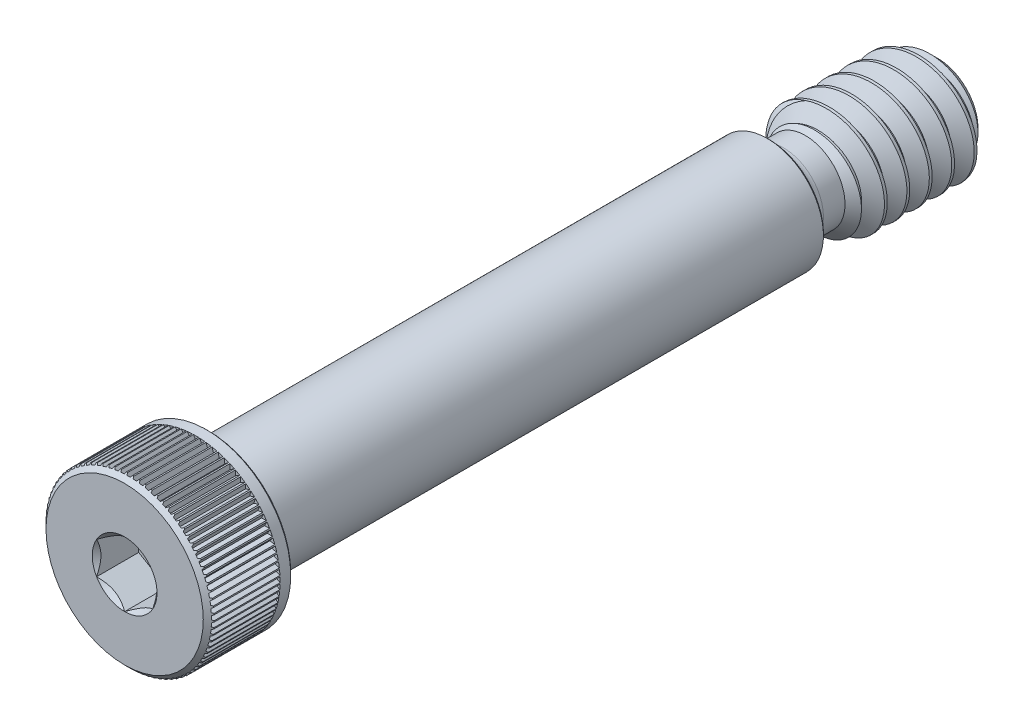
SolidWorks part; units mm, degrees
ref_plane "Front Plane" through (0, 0, 0) normal (0, 0, 1) x (1, 0, 0)
ref_plane "Top Plane" through (0, 0, 0) normal (0, 1, 0) x (1, 0, 0)
ref_plane "Right Plane" through (0, 0, 0) normal (1, 0, 0) x (0, 0, -1)
sketch "Sketch1" plane through (0, 0, 0) normal (1, 0, 0) x (0, 0, -1)
  line L0 (0, 0) -> (9.525, 0) construction
  line L1 (0, 0) -> (-31.75, 0) construction
  line L2 (9.525, 3.175) -> (9.525, -3.175) construction
  line L3 (9.4456, 3.3125) -> (10.7156, 3.3125) construction
  line L4 (10.7156, 3.3125) -> (10.0806, 2.2126) construction
  line L5 (10.0806, 2.2126) -> (9.4456, 3.3125) construction
  line L6 (9.4853, 3.2437) -> (10.6759, 3.2437) construction
  line L7 (9.525, 3.175) -> (10.6363, 3.175) construction
  line L8 (10.0012, 2.3501) -> (10.16, 2.3501) construction
  line L9 (10.0806, 2.3501) -> (10.0806, 2.2126) construction
  line L10 (10.0806, 3.175) -> (10.0806, 3.3125) construction
  line L11 (0, 3.175) -> (0, -3.175) construction
  line L12 (-31.75, 0) -> (-36.5125, 0) construction
  line L13 (-36.5125, 4.7625) -> (-36.5125, -4.7625) construction
  line L14 (-31.75, 4.7625) -> (-31.75, -4.7625) construction
  point P7 (9.525, 0)
  point P12 (6.35, -3.175)
  point P19 (10.0806, 3.2437)
  point P23 (0, 0)
  point P27 (-36.5125, 0)
  point P29 (-31.75, 0)
  point P30 (-36.5125, -1.5875)
  point P31 (-36.5125, 1.5875)
  point P32 (9.525, 3.175)
  point P33 (-34.1313, 0)
  point P34 (9.525, -3.175)
  dimension "Screw Size Decimal Equivalent" = 6.35
  dimension "D1" = 60
  dimension "Pitch" = 1.27
  dimension "D2" = 0.1588
  dimension "Thread Length" = 9.525
  dimension "D3" = 3.175
  dimension "Head Diameter" = 9.525
  dimension "Head Height" = 4.7625
  dimension "Shoulder Length" = 31.75
  dimension "Drive Size" = 3.175
  dimension "D4" = 2.3813
  dimension "Shoulder Diameter" = 6.35
sketch "Sketch2" plane through (0, 0, 0) normal (1, 0, 0) x (0, 0, -1)
  line L0 (0, 3.175) -> (2.9591, 3.175) construction
  line L1 (2.9591, 3.175) -> (2.032, 2.2479) construction
  line L2 (2.032, 2.2479) -> (0, 2.2479) construction
  line L3 (0, 0) -> (9.525, 0) construction
  line L4 (0, 0) -> (9.525, 0) construction
  line L6 (0, 3.175) -> (0, -3.175) construction
  dimension "Thread Neck (Undercut) Width/Length" = 2.032
  dimension "D3" = 45
  dimension "Thread Neck (Undercut) Diameter" = 4.4958
sketch "Sketch3" plane through (0, 0, 0) normal (1, 0, 0) x (0, 0, -1)
  line L0 (-36.5125, 4.4529) -> (-36.2029, 4.7625)
  line L1 (-36.5125, 4.7625) -> (-36.5125, -4.7625) construction
  line L2 (-36.2029, 4.7625) -> (-31.8691, 4.7625)
  line L3 (-31.8691, 4.7625) -> (-31.75, 4.6434)
  line L4 (-31.75, 4.6434) -> (-31.75, 3.175)
  line L5 (-36.5125, 4.4529) -> (-36.5125, 0)
  line L6 (-36.5125, 0) -> (-31.2738, 0)
  line L7 (0, 0) -> (-31.75, 0) construction
  line L8 (-31.2738, 0) -> (-31.2738, 3.175)
  line L9 (-31.2738, 3.175) -> (-31.75, 3.175)
  line L10 (0, 0) -> (-31.75, 0) construction
  dimension "D1" = 45
  dimension "D2" = 0.3096
  dimension "D3" = 45
  dimension "D4" = 0.1191
  dimension "D5" = 0.4763
  dimension "D6" = 6.35
revolve "Revolve1" add sketch "Sketch3" angle 360 about L6
fillet "Fillet1" radius 0.127 1 edges at (3.175, 0, 31.75)
sketch "Sketch4" plane through (0, 0, 0) normal (1, 0, 0) x (0, 0, -1)
  line L0 (-31.2738, 3.175) -> (-0.1191, 3.175)
  line L1 (0, 3.0559) -> (0, 0)
  line L2 (0, 0) -> (-31.2738, 0)
  line L3 (-31.2738, 0) -> (-31.2738, 3.175)
  line L4 (-0.1191, 3.175) -> (0, 3.0559)
  dimension "D1" = 45
  dimension "D2" = 0.1191
revolve "Revolve2" add sketch "Sketch4" angle 360 about L2
sketch "Sketch5" plane through (0, 0, 0) normal (1, 0, 0) x (0, 0, -1)
  line L0 (9.525, 2.286) -> (8.636, 3.175)
  line L1 (9.525, 3.175) -> (9.525, -3.175) construction
  line L2 (8.636, 3.175) -> (2.9591, 3.175)
  line L3 (2.9591, 3.175) -> (2.032, 2.2479)
  line L4 (2.032, 2.2479) -> (0.808, 2.2479)
  line L5 (0, 3.0559) -> (0, 0)
  line L6 (0, 3.175) -> (0, -3.175) construction
  line L7 (0, 0) -> (9.525, 0)
  line L8 (9.525, 0) -> (9.525, 2.286)
  line L9 (2.032, 2.2479) -> (0, 2.2479) construction
  arc A1 (0.808, 2.2479) -> (0, 3.0559) centre (0.808, 3.0559) cw
  dimension "D1" = 45
  dimension "D2" = 0.889
revolve "Revolve3" add sketch "Sketch5" angle 360 about L7
sketch "Sketch6" plane through (0, 0, 36.5125) normal (0, 0, 1) x (1, 0, 0)
  line L1 (-1.5875, 0.9165) -> (-1.5875, -0.9165)
  line L2 (-1.5875, -0.9165) -> (0, -1.8331)
  line L3 (0, -1.8331) -> (1.5875, -0.9165)
  line L4 (1.5875, -0.9165) -> (1.5875, 0.9165)
  line L5 (1.5875, 0.9165) -> (0, 1.8331)
  line L6 (0, 1.8331) -> (-1.5875, 0.9165)
  circle A0 centre (0, 0) radius 1.5875 construction
extrude "Cut-Extrude1" cut sketch "Sketch6" against normal up to vertex (2.3813 mm away) up to point (0, 0, 34.1313)
sketch "Sketch7" plane through (0, 0, 36.5125) normal (0, 0, 1) x (1, 0, 0)
  circle A0 centre (0, 0) radius 1.8331
extrude "Cut-Extrude2" cut sketch "Sketch7" against normal up to vertex (2.3813 mm away) draft 45 up to point (0, 0, 34.1313)
sketch "Sketch11" plane through (0, 0, 34.1313) normal (0, 0, 1) x (1, 0, 0)
  line L1 (-0.5556, 0.3208) -> (-0.5556, -0.3208)
  line L2 (-0.5556, -0.3208) -> (0, -0.6416)
  line L3 (0, -0.6416) -> (0.5556, -0.3208)
  line L4 (0.5556, -0.3208) -> (0.5556, 0.3208)
  line L5 (0.5556, 0.3208) -> (0, 0.6416)
  line L6 (0, 0.6416) -> (-0.5556, 0.3208)
  circle A0 centre (0, 0) radius 0.5556 construction
  dimension "D1" = 1.1113
extrude "Cut-Extrude4" cut sketch "Sketch11" against normal blind 1.1906 draft 45
sketch "Sketch12" plane through (0, 0, 0) normal (1, 0, 0) x (0, 0, -1)
  line L0 (-23.8125, 4.7625) -> (-23.8125, -4.7625) construction
  line L2 (-7.9375, 4.7625) -> (-7.9375, -4.7625) construction
  line L4 (-31.75, 4.7625) -> (-31.75, -4.7625) construction
  line L5 (0, 0) -> (-31.75, 0) construction
  line L7 (0, 3.175) -> (0, -3.175) construction
  point P3 (-23.8125, 0)
  point P6 (-7.9375, 0)
  dimension "D1" = 7.9375
  dimension "D2" = 7.9375
sketch "Sketch13" plane through (0, 0, 0) normal (0, 0, 1) x (1, 0, 0)
  circle A0 centre (0, 0) radius 4.7625 construction
sketch "Sketch8" plane through (0, 0, 0) normal (1, 0, 0) x (0, 0, -1)
  line L0 (9.4853, 3.2437) -> (10.6759, 3.2437)
  line L1 (10.6759, 3.2437) -> (10.16, 2.3501)
  line L2 (10.16, 2.3501) -> (10.0012, 2.3501)
  line L3 (10.0012, 2.3501) -> (9.4853, 3.2437)
sketch "Sketch9" plane through (0, 0, -9.525) normal (0, 0, -1) x (-1, 0, 0)
  circle A0 centre (0, 0) radius 3.175
curve "Helix/Spiral1" pitch 1.27 height 9.525 radius 3.175 centre (0, 0, -9.525) axis (0, 0, 1) start towards (0, 1, 0)
sweep "Cut-Sweep1" cut profiles "Sketch8" path "Helix/Spiral1"
ref_plane "Plane1" through (0, 0, 36.2803) normal (0, 0, 1) x (1, 0, 0)
sketch "Sketch10" plane through (0, 0, 36.2803) normal (0, 0, 1) x (1, 0, 0)
  line L0 (-0.143, 4.7625) -> (0.143, 4.7625)
  line L1 (-0.143, 4.7625) -> (0, 4.5149)
  line L2 (0, 4.5149) -> (0.143, 4.7625)
  line L3 (-0.143, 4.7625) -> (0, 0) construction
  line L4 (0, 0) -> (0.143, 4.7625) construction
  circle A0 centre (0, 0) radius 4.5149 construction
  point P7 (0, 4.7625)
  dimension "D1" = 0.2476
  dimension "D2" = 3.439
extrude "Cut-Extrude3" cut sketch "Sketch10" against normal blind 3.81
pattern_circular "CirPattern1" count 85 over 360 about axis through (0, 0, 31.75) along (0, 0, 1) of "Cut-Extrude3" reverse direction yes
equation "\"D2@Sketch1\"=\"Pitch@Sketch1\"/8"
equation "\"D3@Sketch1\"=\"Pitch@Sketch1\"*2.5"
equation "\"D4@Sketch1\"=\"Head Height@Sketch1\"*.5"
equation "\"D2@Sketch3\"=\"Head Height@Sketch1\" * .065"
equation "\"D4@Sketch3\" = \"Head Height@Sketch1\" * .025"
equation "\"D5@Sketch3\"=\"Head Height@Sketch1\"*.1"
equation "\"D1@Fillet1\"=\"Shoulder Diameter@Sketch1\"*.02"
equation "\"D2@Sketch5\"=\"Pitch@Sketch1\"*.7"
equation "\"D2@Sketch4\"=\"D4@Sketch3\""
equation "\"D3@Helix/Spiral1\"=\"Thread Length@Sketch1\""
equation "\"D4@Helix/Spiral1\"=\"Pitch@Sketch1\""
equation "\"D1@Sketch10\"=\"D2@Sketch3\"*.8"
equation "\"D1@Cut-Extrude3\"=\"Head Height@Sketch1\"*.8"
equation "\"D1@CirPattern1\"=(360/\"D2@Sketch10\")-20"
equation "\"D1@Plane1\"=\"D2@Sketch3\"*.75"
equation "\"D1@Sketch11\"=\"Drive Size@Sketch1\"*.35"
equation "\"D1@Cut-Extrude4\"=\"Head Height@Sketch1\"*.25"
equation "\"D1@Sketch12\"=\"Shoulder Length@Sketch1\"*.25"
equation "\"D2@Sketch12\"=\"D1@Sketch12\""
equation "\"D6@Sketch3\"=\"Shoulder Diameter@Sketch1\""
